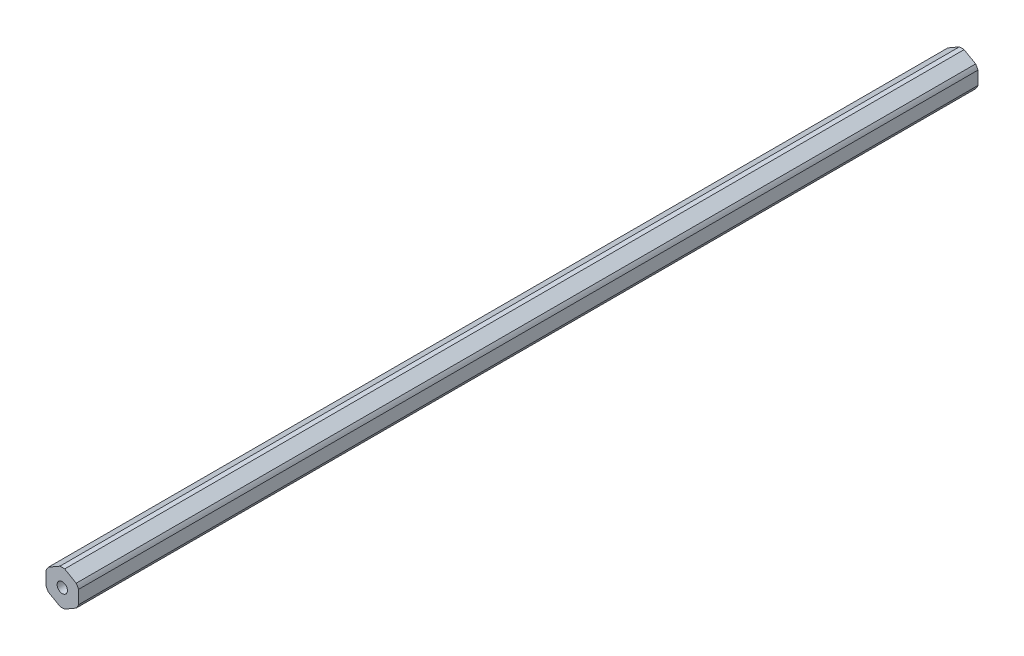
SolidWorks part; units mm, degrees
ref_plane "Front Plane" through (0, 0, 0) normal (0, 0, 1) x (1, 0, 0)
ref_plane "Top Plane" through (0, 0, 0) normal (0, 1, 0) x (1, 0, 0)
ref_plane "Right Plane" through (0, 0, 0) normal (1, 0, 0) x (0, 0, -1)
sketch "Sketch1" plane through (0, 0, 0) normal (0, 0, 1) x (1, 0, 0)
  line L1 (0, 7.3323) -> (-6.35, 3.6662)
  line L2 (-6.35, 3.6662) -> (-6.35, -3.6662)
  line L3 (-6.35, -3.6662) -> (0, -7.3323)
  line L4 (0, -7.3323) -> (6.35, -3.6662)
  line L5 (6.35, -3.6662) -> (6.35, 3.6662)
  line L6 (6.35, 3.6662) -> (0, 7.3323)
  circle A0 centre (0, 0) radius 6.35 construction
  circle A1 centre (0, 0) radius 6.858
  dimension "D1" = 12.7
  dimension "D2" = 13.716
extrude "Boss-Extrude1" add sketch "Sketch1" along normal mid plane 350.8375 contours L5 A1 L6 L1 L2 L3 L4 region at (0, 0, 0)
hole_wizard "#10-32 Tapped Hole1" positions "3DSketch1" profile "Sketch2" tap size "#10-32" standard "ANSI Inch"
sketch3d "3DSketch1"
  line L0 (0, 0, 175.4187) -> (0, 0, -175.4187) construction
  line L1 (0, 0, 175.4187) -> (0, 0, -175.4187) construction
  point P0 (0, 0, 175.4187)
  point P4 (0, 0, -175.4187)
sketch "Sketch2" plane through (0, 0, 175.4187) normal (1, 0, 0) x (0, -1, 0)
  line L0 (0, 0) -> (0, 17.5608)
  line L1 (0, 17.5608) -> (2.0193, 16.3474)
  line L2 (2.0193, 16.3474) -> (2.0193, 0)
  line L5 (2.0193, 0) -> (0, 0)
  line L10 (0, 17.5608) -> (-2.0193, 16.3474) construction
  line L11 (0, -6.35) -> (0, 107.95) construction
  dimension "Tap Drill Dia." = 4.0386
  dimension "Tap Drill Depth" = 16.3474
  dimension "Drill Angle" = 118
cosmetic thread "Hole Thread1" parameters "D1"=13.97, "D2"=4.826
cosmetic thread "Hole Thread2" parameters "D1"=13.97, "D2"=4.826
